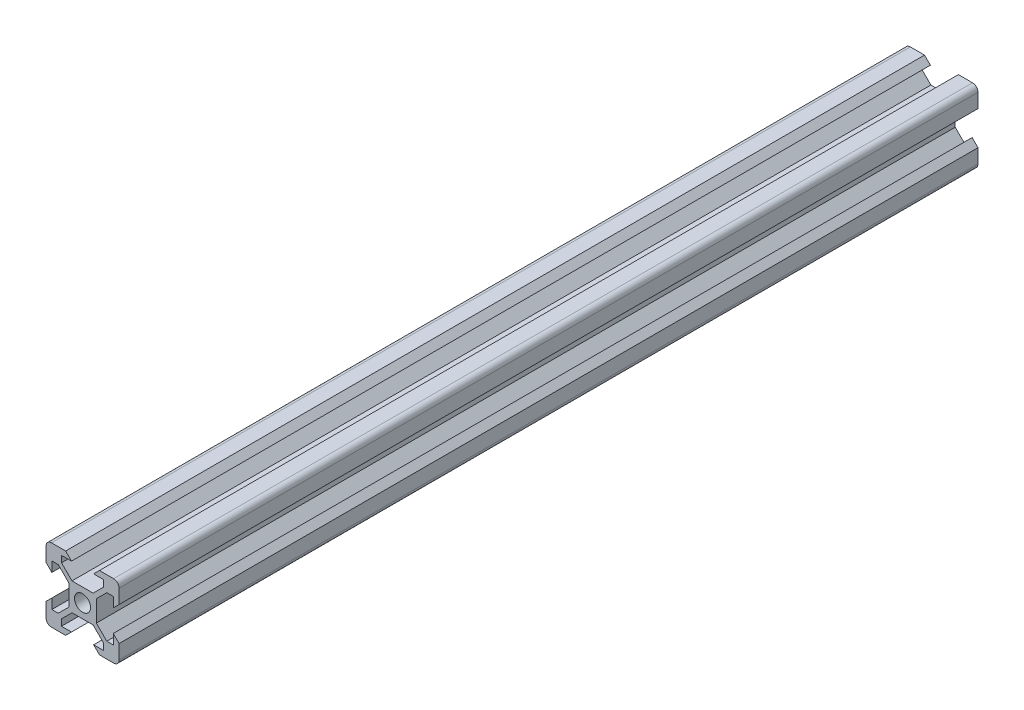
SolidWorks part; units mm, degrees
ref_plane "Front Plane" through (0, 0, 0) normal (0, 0, 1) x (1, 0, 0)
ref_plane "Top Plane" through (0, 0, 0) normal (0, 1, 0) x (1, 0, 0)
ref_plane "Right Plane" through (0, 0, 0) normal (1, 0, 0) x (0, 0, -1)
sketch "Sketch1" plane through (0, 0, 0) normal (0, 0, 1) x (1, 0, 0)
  line L0 (-5.7847, 7.544) -> (-11.512, 13.2713)
  line L1 (-7.544, 7.544) -> (7.544, 7.544)
  line L2 (-7.544, 7.544) -> (-7.544, -7.544)
  line L3 (-7.544, -7.544) -> (7.544, -7.544)
  line L4 (7.544, 7.544) -> (7.544, -7.544)
  line L5 (-7.544, 7.544) -> (7.544, -7.544) construction
  line L6 (-7.544, -7.544) -> (7.544, 7.544) construction
  line L7 (-11.512, 13.2713) -> (-11.512, 16.8)
  line L8 (-11.512, 16.8) -> (-6.052, 16.8)
  line L9 (-6.052, 16.8) -> (-9.252, 20)
  line L10 (-9.252, 20) -> (-17, 20)
  line L11 (-20, 17) -> (-20, 9.252)
  line L12 (-20, 9.252) -> (-16.8, 6.052)
  line L13 (-16.8, 6.052) -> (-16.8, 11.512)
  line L14 (-16.8, 11.512) -> (-13.2713, 11.512)
  line L15 (-13.2713, 11.512) -> (-7.544, 5.7847)
  line L16 (-19.1213, 19.1213) -> (0, 0) construction
  line L17 (13.2713, 11.512) -> (16.8, 11.512)
  line L18 (20, 9.252) -> (20, 17)
  line L19 (17, 20) -> (9.252, 20)
  line L20 (9.252, 20) -> (6.052, 16.8)
  line L21 (6.052, 16.8) -> (11.512, 16.8)
  line L22 (11.512, 16.8) -> (11.512, 13.2713)
  line L23 (11.512, 13.2713) -> (5.7847, 7.544)
  line L24 (7.544, 5.7847) -> (13.2713, 11.512)
  line L25 (16.8, 11.512) -> (16.8, 6.052)
  line L26 (16.8, 6.052) -> (20, 9.252)
  line L27 (19.1213, 19.1213) -> (0, 0) construction
  line L28 (11.512, -13.2713) -> (11.512, -16.8)
  line L29 (9.252, -20) -> (17, -20)
  line L30 (20, -17) -> (20, -9.252)
  line L31 (20, -9.252) -> (16.8, -6.052)
  line L32 (16.8, -6.052) -> (16.8, -11.512)
  line L33 (16.8, -11.512) -> (13.2713, -11.512)
  line L34 (13.2713, -11.512) -> (7.544, -5.7847)
  line L35 (5.7847, -7.544) -> (11.512, -13.2713)
  line L36 (11.512, -16.8) -> (6.052, -16.8)
  line L37 (6.052, -16.8) -> (9.252, -20)
  line L38 (19.1213, -19.1213) -> (0, 0) construction
  line L39 (-13.2713, -11.512) -> (-16.8, -11.512)
  line L40 (-20, -9.252) -> (-20, -17)
  line L41 (-17, -20) -> (-9.252, -20)
  line L42 (-9.252, -20) -> (-6.052, -16.8)
  line L43 (-6.052, -16.8) -> (-11.512, -16.8)
  line L44 (-11.512, -16.8) -> (-11.512, -13.2713)
  line L45 (-11.512, -13.2713) -> (-5.7847, -7.544)
  line L46 (-7.544, -5.7847) -> (-13.2713, -11.512)
  line L47 (-16.8, -11.512) -> (-16.8, -6.052)
  line L48 (-16.8, -6.052) -> (-20, -9.252)
  line L49 (-19.1213, -19.1213) -> (0, 0) construction
  circle A0 centre (0, 0) radius 4.4
  arc A1 (-17, 20) -> (-20, 17) centre (-17, 17) ccw
  arc A2 (20, 17) -> (17, 20) centre (17, 17) ccw
  arc A3 (17, -20) -> (20, -17) centre (17, -17) ccw
  arc A4 (-20, -17) -> (-17, -20) centre (-17, -17) ccw
  point P66 (0, 0)
  dimension "D1" = 8.8
  dimension "D8" = 3
  dimension "D2" = 15.088
  dimension "D3" = 2.488
  dimension "D4" = 8.488
  dimension "D5" = 3.2
  dimension "D6" = 20
  dimension "D7" = 15.2
  dimension "D9" = 4
extrude "Boss-Extrude1" add sketch "Sketch1" along normal mid plane 470 contours L10 A1 L11 L12 L13 L14 L15 L2 L1 L0 L7 L8 L9 | L18 A2 L19 L20 L21 L22 L23 L1 L4 L24 L17 L25 L26 | L40 A4 L41 L42 L43 L44 L45 L3 L2 L46 L39 L47 L48 | L29 A3 L30 L31 L32 L33 L34 L4 L3 L35 L28 L36 L37 | L4 L1 L2 L3 A0 region at (-14.3184, 14.3184, 0) region at (0, 7.3306, 0) region at (14.3184, 14.3184, 0) region at (-14.3184, -14.3184, 0) region at (14.3184, -14.3184, 0)
equation "\"longitud\"= 800"
